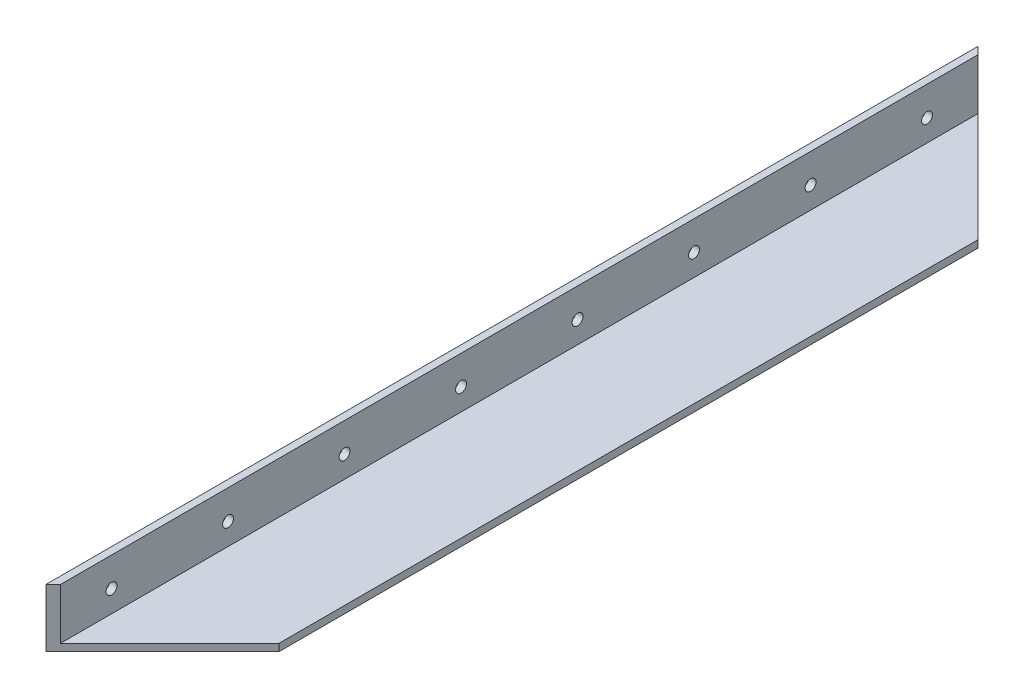
SolidWorks part; units mm, degrees
material "6063-T1"
ref_plane "Front Plane" through (0, 0, 0) normal (0, 0, 1) x (1, 0, 0)
ref_plane "Top Plane" through (0, 0, 0) normal (0, 1, 0) x (1, 0, 0)
ref_plane "Right Plane" through (0, 0, 0) normal (1, 0, 0) x (0, 0, -1)
sketch "Sketch1" plane through (0, 0, 0) normal (0, 0, 1) x (1, 0, 0)
  line L1 (0, 0) -> (50.8, 0)
  line L2 (0, 0) -> (0, 25.4)
  line L3 (0, 25.4) -> (50.8, 25.4)
  line L4 (50.8, 0) -> (50.8, 25.4)
  line L5 (50.8, 25.4) -> (3.175, 25.4)
  line L6 (50.8, 25.4) -> (50.8, 3.175)
  line L7 (50.8, 3.175) -> (3.175, 3.175)
  line L8 (3.175, 25.4) -> (3.175, 3.175)
  dimension "D1" = 3.175
  dimension "D2" = 3.175
  dimension "D3" = 25.4
  dimension "D4" = 50.8
extrude "Boss-Extrude1" add sketch "Sketch1" along normal blind 406.4 contours L8 L3 L2 L1 L4 L7 region at (0.568, 12.7, 0)
sketch "Sketch2" plane through (0, 0, 0) normal (-1, 0, 0) x (0, 0, 1)
  line L0 (406.4, 0) -> (0, 0) construction
  line L1 (406.4, 0) -> (406.4, 25.4) construction
  circle A0 centre (381, 12.7) radius 2.3813
  circle A1 centre (330.2, 12.7) radius 2.3813
  circle A2 centre (279.4, 12.7) radius 2.3813
  circle A3 centre (228.6, 12.7) radius 2.3813
  circle A4 centre (177.8, 12.7) radius 2.3813
  circle A5 centre (127, 12.7) radius 2.3813
  circle A6 centre (76.2, 12.7) radius 2.3813
  circle A7 centre (25.4, 12.7) radius 2.3813
  circle A8 centre (-25.4, 12.7) radius 2.3813
  circle A9 centre (-76.2, 12.7) radius 2.3813
  dimension "D3" = 4.7625
  dimension "D1" = 12.7
  dimension "D2" = 25.4
  dimension "D4" = 10
extrude "Cut-Extrude1" cut sketch "Sketch2" against normal through all
chamfer "Chamfer1" distance 50.8 angle 45 1 edges at (50.8, 1.5875, 406.4)
chamfer "Chamfer2" distance 50.8 angle 45 1 edges at (50.8, 1.5875, 0)
